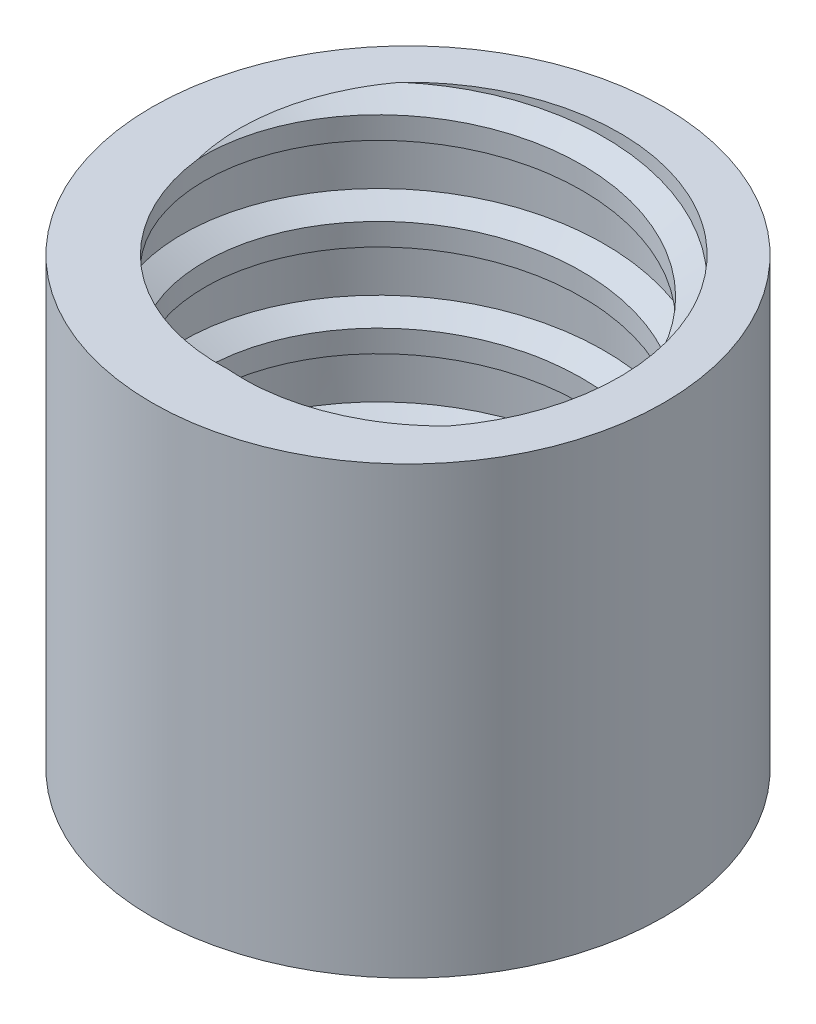
SolidWorks part; units mm, degrees
ref_plane "Front" through (0, 0, 0) normal (0, 0, 1) x (1, 0, 0)
ref_plane "Top" through (0, 0, 0) normal (0, 1, 0) x (1, 0, 0)
ref_plane "Right" through (0, 0, 0) normal (1, 0, 0) x (0, 0, -1)
sketch "Sketch1" plane through (0, 0, 0) normal (0, 1, 0) x (1, 0, 0)
  circle A1 centre (0, 0) radius 8.5
  circle A3 centre (0, 0) radius 11.5
  dimension "D1" = 17
  dimension "D2" = 23
extrude "Boss-Extrude1" add sketch "Sketch1" along normal blind 20
ref_axis "Axis1" through (0, 20, 0) along (0, -1, 0)
ref_plane "Plane1" through (0, -5, 0) normal (0, -1, 0) x (-1, 0, 0)
sketch "Sketch3" plane through (0, 0, 0) normal (0, 0, 1) x (1, 0, 0)
  line L4 (-8.5, -4.9755) -> (-8.5, -1.8208)
  line L6 (-8.5, -4.9755) -> (-9.5, -4.3982)
  line L7 (-9.5, -4.3982) -> (-9.5, -2.3982)
  line L8 (-9.5, -2.3982) -> (-8.5, -1.8208)
  dimension "D1" = 8.5
  dimension "D2" = 9.5
  dimension "D3" = 1.8208
  dimension "D4" = 2.3982
  dimension "D5" = 4.3982
sketch "Sketch6" plane through (0, 0, 0) normal (0, -1, 0) x (1, 0, 0)
  circle A0 centre (0, 0) radius 8
  circle A2 centre (0, 0) radius 11.5 construction
  dimension "D1" = 16
curve "Helix/Spiral1" pitch 4.15 height 40.4625 radius 8 centre (0, 0, 0) axis (0, 1, 0) start towards (0, 0, -1)
sweep "Cut-Sweep1" cut profiles "Sketch3" path "Helix/Spiral1"
